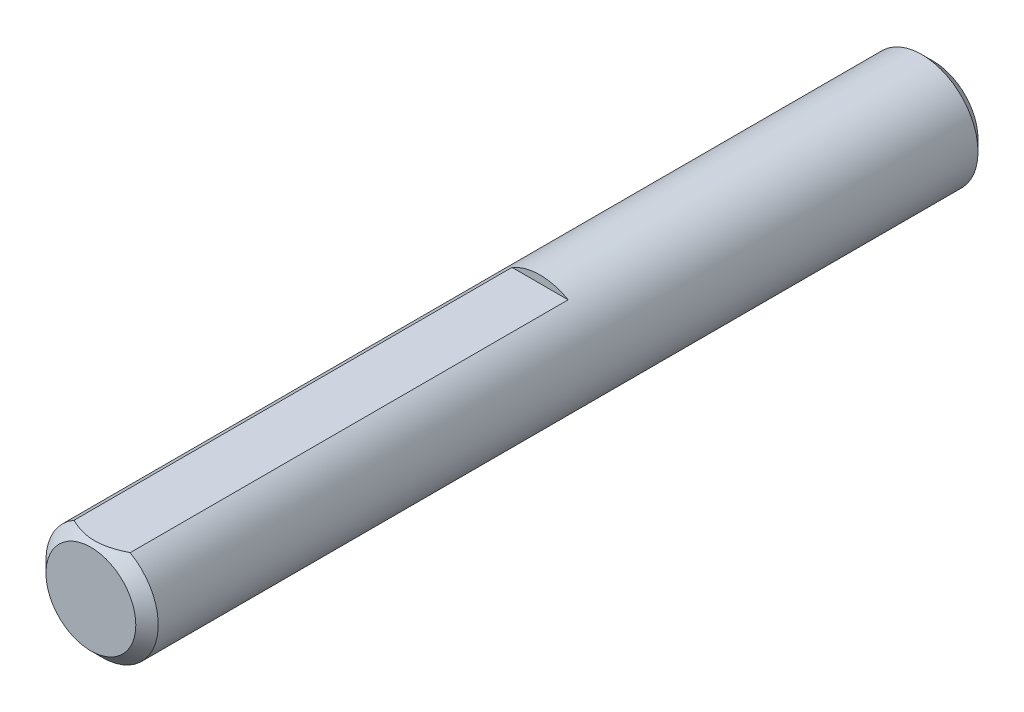
SolidWorks part; units mm, degrees
ref_plane "Front" through (0, 0, 0) normal (0, 0, 1) x (1, 0, 0)
ref_plane "Top" through (0, 0, 0) normal (0, 1, 0) x (1, 0, 0)
ref_plane "Right" through (0, 0, 0) normal (1, 0, 0) x (0, 0, -1)
sketch "Sketch1" plane through (0, 0, 0) normal (0, 0, 1) x (1, 0, 0)
  circle A0 centre (0, 0) radius 3.175
  dimension "D1" = 6.35
extrude "Extrude1" add sketch "Sketch1" along normal mid plane 47.625
chamfer "Chamfer1" distance 0.635 angle 45 2 edges at (3.175, 0, -23.8125) (3.175, 0, 23.8125)
ref_plane "Plane1" through (0, 0, -1.5875) normal (0, 0, 1) x (1, 0, 0)
sketch "Sketch13" plane through (0, 0, -1.5875) normal (0, 0, 1) x (1, 0, 0)
  line L3 (-1.5875, 2.7496) -> (1.5875, 2.7496)
  circle A0 centre (0, 0) radius 3.175 construction
  arc A1 (1.5875, 2.7496) -> (-1.5875, 2.7496) centre (0, 0) ccw
  dimension "D1" = 3.175
extrude "Extrude7" cut sketch "Sketch13" along normal through all
equation "\"D1@Chamfer1\" = \"D1@Sketch1\" * .1"
equation "\"D1@Sketch13\" = \"D1@Sketch1\" * .5"
